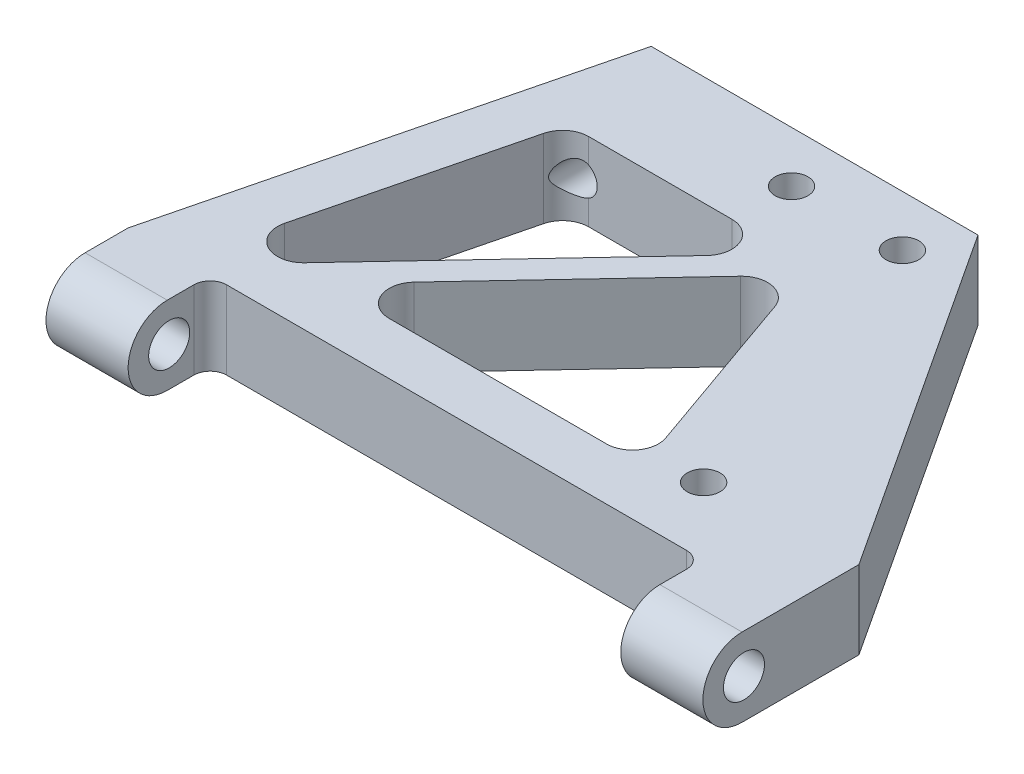
SolidWorks part; units mm, degrees
material "6061-T6 (SS)"
ref_plane "Front Plane" through (0, 0, 0) normal (0, 0, 1) x (1, 0, 0)
ref_plane "Top Plane" through (0, 0, 0) normal (0, 1, 0) x (1, 0, 0)
ref_plane "Right Plane" through (0, 0, 0) normal (1, 0, 0) x (0, 0, -1)
sketch "Sketch1" plane through (0, 0, 0) normal (0, 1, 0) x (1, 0, 0)
  line L3 (0, -122) -> (20, -122)
  line L5 (20, -122) -> (346.4065, -122) construction
  line L7 (140, -106) -> (140, -122)
  line L9 (140, -122) -> (160, -122)
  line L10 (136, -102) -> (24, -102)
  line L12 (20, -106) -> (20, -122)
  line L16 (160, -122) -> (160, -84)
  line L20 (24, -102) -> (0, -102) construction
  line L21 (0, 0) -> (0, -102) construction
  line L22 (0, -102) -> (25.4, 0)
  line L23 (0, -102) -> (0, -122)
  line L24 (105, 0) -> (25.4, 0)
  line L25 (105, 0) -> (160, -84)
  line L36 (-14.04, -12.4142) -> (141.5, -12.4142) construction
  line L41 (0, 0) -> (25.4, 0) construction
  line L42 (-24.6497, -112) -> (196.247, -112) construction
  arc A3 (136, -102) -> (140, -106) centre (136, -106) cw
  arc A4 (24, -102) -> (20, -106) centre (24, -106) ccw
  circle A5 centre (99, -12.4142) radius 4
  circle A6 centre (72, -12.4142) radius 4
  point P19 (34.925, 30)
  point P22 (140, -102)
  point P25 (20, -102)
  point P30 (25.4, 0)
  point P33 (0, 0)
  dimension "D7" = 105
  dimension "D9" = 112
  dimension "D10" = 4
  dimension "D11" = 10
  dimension "D12" = 8
  dimension "D13" = 27
  dimension "D15" = 12.4142
  dimension "D2" = 25.4
  dimension "D3" = 20
  dimension "D4" = 140
  dimension "D5" = 20
  dimension "D6" = 34.925
  dimension "D8" = 30
  dimension "D14" = 38
  dimension "D16" = 72
extrude "Boss-Extrude1" add sketch "Sketch1" along normal blind 19.05 contours L3 | A4 L10 L3 L12 | L10 A3 L7 L9 L16 | L16 L25 L24 L22 L23 L3 L12 A4 L10 A3 L7 L9 region at (76.2492, 0, 60.5513)
sketch "Sketch7" plane through (0, 0, 0) normal (0, 0, -1) x (-1, 0, 0)
  line L0 (-34.925, 9.525) -> (0, 9.525) construction
  line L3 (0, 19.05) -> (0, 0) construction
  circle A0 centre (-34.925, 9.525) radius 3.9687
  dimension "D1" = 7.9375
  dimension "D2" = 34.925
extrude "Cut-Extrude7" cut sketch "Sketch7" against normal blind 38.1
fillet "Fillet6" 2 edges at (10, 19.05, 122) (10, 0, 122) type full round first side face at (77.5333, 19.05, 90.6953) second side face at (77.5333, 0, 90.6953) middle face at (10, 9.525, 122)
fillet "Fillet7" 2 edges at (150, 19.05, 122) (150, 0, 122) type full round first side face at (77.5333, 19.05, 89.1078) second side face at (77.5333, 0, 89.1078) middle face at (150, 9.525, 122)
sketch "Sketch27" plane through (0, 0, 0) normal (-1, 0, 0) x (0, 0, 1)
  line L0 (112, 0) -> (112, 19.05) construction
  line L1 (102, 0) -> (122, 0) construction
  line L2 (102, 19.05) -> (112.475, 19.05) construction
  circle A0 centre (112, 9.525) radius 5
  point P12 (112, 9.525)
  dimension "D1" = 10
extrude "Cut-Extrude16" cut sketch "Sketch27" against normal through all
sketch "Sketch28" plane through (0, 0, 0) normal (1, 0, 0) x (0, 0, -1)
  line L0 (-112, -190.4281) -> (-112, 209.4781) construction
  line L1 (-12.4142, 100.6714) -> (-112, 209.4781) construction
  line L2 (-12.4142, -81.6214) -> (-112, -190.4281) construction
  line L3 (-112, 9.525) -> (23, 9.525) construction
  line L4 (-112, 9.525) -> (-210.4838, 111.8233) construction
  line L5 (-210.4838, 111.8233) -> (-316.7444, 9.525) construction
  line L6 (-112, 9.525) -> (-316.7444, 9.525) construction
  line L7 (0, 35.7967) -> (-207.2867, 123.3896) construction
  line L8 (0, 19.05) -> (-84, 19.05) construction
  line L9 (0, 35.7967) -> (0, 19.05) construction
  line L11 (-112.475, 19.05) -> (-84, 19.05) construction
  line L12 (-92.1423, 19.05) -> (-214.5123, 100.5197) construction
  circle A1 centre (-112, 9.525) radius 135 construction
  circle A3 centre (-12.4142, 100.6714) radius 4
  circle A4 centre (-12.4142, -81.6214) radius 4
  circle A5 centre (-112, 9.525) radius 142 construction
  circle A6 centre (-210.4838, 111.8233) radius 12 construction
  point P12 (-112, 9.525)
  dimension "D1" = 135
  dimension "D4" = 8
  dimension "D6" = 142
  dimension "D9" = 24
  dimension "D2" = 147.5
  dimension "D3" = 199.9531
  dimension "D5" = 81.6214
  dimension "D7" = 147.5
  dimension "D8" = 204.7444
sketch3d "3DSketch1"
  line L0 (160, 9.525, 112) -> (0, 9.525, 112) construction
  line L1 (160, 9.525, 112) -> (140, 9.525, 112) construction
  line L2 (20, 9.525, 112) -> (0, 9.525, 112) construction
sketch "Sketch29" plane through (0, 0, 0) normal (0, -1, 0) x (1, 0, 0)
  line L0 (0, 12.4142) -> (133.1578, 12.4142) construction
  line L1 (0, 8.4142) -> (0, 16.4142) construction
sketch "Sketch30" plane through (0, 0, 0) normal (0, -1, 0) x (1, 0, 0)
  circle A0 centre (72, 12.4142) radius 4 construction
  circle A1 centre (99, 12.4142) radius 4 construction
  circle A2 centre (72, 12.4142) radius 4
  circle A3 centre (99, 12.4142) radius 4
extrude "Cut-Extrude17" cut sketch "Sketch30" against normal through all
sketch "Sketch31" plane through (0, 19.05, 0) normal (0, 1, 0) x (1, 0, 0)
  line L1 (0, 0) -> (25.4, 0) construction
  line L2 (0, 0) -> (0, -102) construction
  circle A0 centre (123.7506, -85.5773) radius 4
  dimension "D1" = 8
  dimension "D2" = 85.5773
  dimension "D3" = 123.7506
extrude "Cut-Extrude18" cut sketch "Sketch31" against normal through all
sketch "Sketch32" plane through (0, 19.05, 0) normal (0, 1, 0) x (1, 0, 0)
  line L10 (140, -106) -> (140, -112.475)
  line L11 (140, -112.475) -> (160, -112.475)
  line L12 (160, -112.475) -> (160, -84)
  line L13 (160, -84) -> (105, 0)
  line L14 (105, 0) -> (25.4, 0)
  line L15 (25.4, 0) -> (0, -102)
  line L16 (0, -102) -> (0, -112.475)
  line L17 (0, -112.475) -> (20, -112.475)
  line L18 (20, -112.475) -> (20, -106)
  line L19 (24, -102) -> (136, -102)
  line L20 (140, -106) -> (140, -112.475)
  line L21 (140, -112.475) -> (160, -112.475)
  line L22 (160, -112.475) -> (160, -84)
  line L23 (160, -84) -> (105, 0)
  line L24 (105, 0) -> (25.4, 0)
  line L25 (25.4, 0) -> (0, -102)
  line L26 (0, -102) -> (0, -112.475)
  line L27 (0, -112.475) -> (20, -112.475)
  line L28 (20, -112.475) -> (20, -106)
  line L29 (24, -102) -> (136, -102)
  line L30 (30.6562, -31.4499) -> (18.0779, -81.961)
  line L31 (36.818, -26.6343) -> (71.6779, -26.6343)
  line L33 (95.3627, -39.863) -> (109.7799, -80.8426)
  line L34 (112.7553, -89.3) -> (50.8861, -89.3)
  line L35 (50.8861, -89.3) -> (112.7553, -89.3)
  line L36 (50.8861, -89.3) -> (112.7553, -89.3)
  line L37 (76.3067, -37.3314) -> (28.8685, -87.8425)
  line L38 (84.7439, -37.6233) -> (46.2574, -78.6029)
  line L39 (50.8861, -89.3) -> (103.7898, -89.3)
  arc A2 (24, -102) -> (20, -106) centre (24, -106) ccw
  arc A3 (140, -106) -> (136, -102) centre (136, -106) ccw
  arc A4 (24, -102) -> (20, -106) centre (24, -106) ccw
  arc A5 (140, -106) -> (136, -102) centre (136, -106) ccw
  arc A6 (109.7799, -80.8426) -> (103.7898, -89.3) centre (103.7898, -82.95) cw
  arc A7 (95.3627, -39.863) -> (84.7439, -37.6233) centre (89.3726, -41.9704) ccw
  arc A8 (46.2574, -78.6029) -> (50.8861, -89.3) centre (50.8861, -82.95) ccw
  arc A9 (28.8685, -87.8425) -> (18.0779, -81.961) centre (24.2398, -83.4954) cw
  arc A10 (30.6562, -31.4499) -> (36.818, -26.6343) centre (36.818, -32.9843) cw
  arc A11 (71.6779, -26.6343) -> (76.3067, -37.3314) centre (71.6779, -32.9843) cw
  point P6 (24, -89.3)
  point P8 (136, -89.3)
  point P21 (35.3253, -12.7)
  point P23 (15.7005, -91.5084)
  dimension "D2" = 6.35
  dimension "D3" = 12.7
  dimension "D1" = 0
extrude "Cut-Extrude19" cut sketch "Sketch32" against normal through all contours A11 L31 A10 L30 A9 L37 | L38 A8 L36 A6 L33 A7 region at (43.9152, 19.05, 51.4757) region at (80.7145, 19.05, 69.4296)
